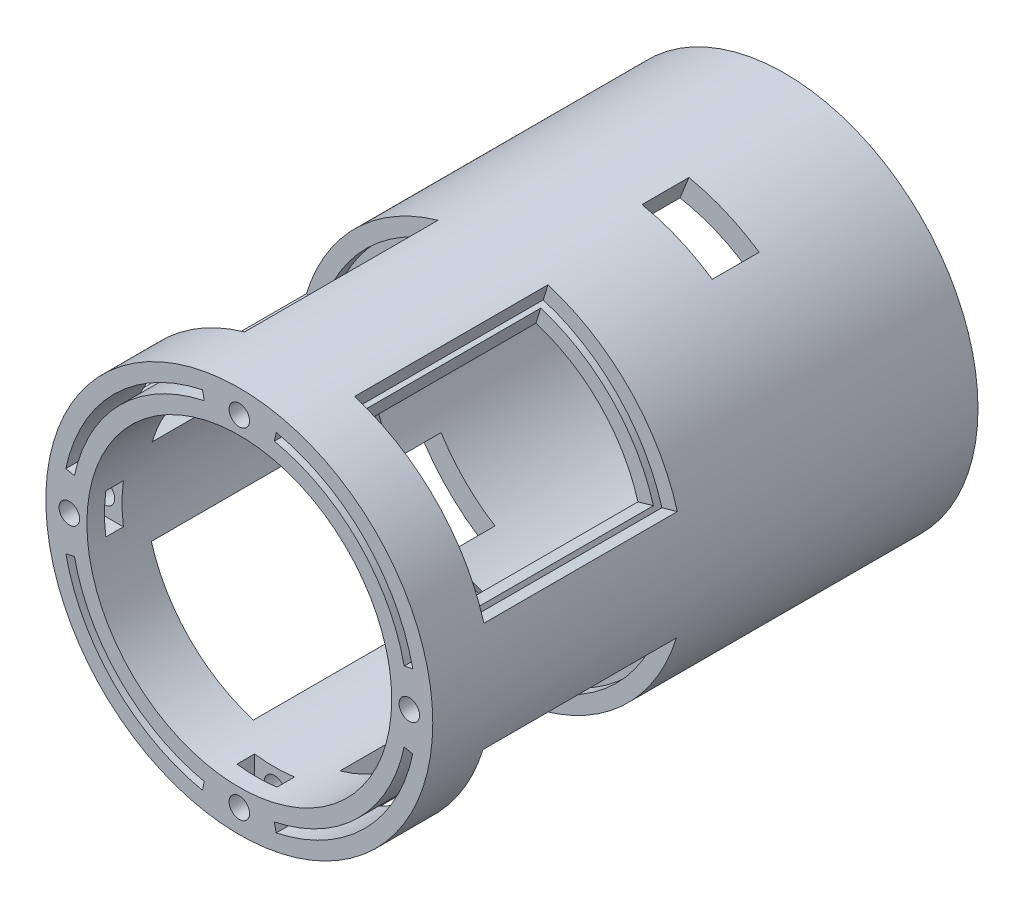
SolidWorks part; units mm, degrees
material "PEI"
ref_plane "Alzado" through (0, 0, 0) normal (0, 0, 1) x (1, 0, 0)
ref_plane "Planta" through (0, 0, 0) normal (0, 1, 0) x (1, 0, 0)
ref_plane "Vista lateral" through (0, 0, 0) normal (1, 0, 0) x (0, 0, -1)
sketch "Croquis1" plane through (0, 0, 0) normal (0, 0, 1) x (1, 0, 0)
  circle A0 centre (0, 0) radius 33
  circle A1 centre (0, 0) radius 29
  dimension "D1" = 66
  dimension "D2" = 4
extrude "Boss-Extrude1" add sketch "Croquis1" along normal blind 93
ref_axis "Eje1" through (0, 0, 93) along (0, 0, -1)
ref_plane "Plano2" through (0, 0, 0) normal (0.9563, -0.2924, 0) x (0, 0, -1)
sketch "Sketch8" plane through (0, 0, 0) normal (0, 0, -1) x (-1, 0, 0)
  arc A0 (-4, -28.7228) -> (4, -28.7228) centre (0, 0) ccw
  circle A1 centre (0, 0) radius 29 construction
  arc A2 (-4, -28.7228) -> (4, -28.7228) centre (0, -30.3008) cw
  arc A3 (-28.7228, 4) -> (-28.7228, -4) centre (0, 0) ccw
  arc A4 (-28.7228, 4) -> (-28.7228, -4) centre (-30.3008, 0) cw
  arc A5 (4, 28.7228) -> (-4, 28.7228) centre (0, 0) ccw
  arc A6 (4, 28.7228) -> (-4, 28.7228) centre (0, 30.3008) cw
  arc A7 (28.7228, -4) -> (28.7228, 4) centre (0, 0) ccw
  arc A8 (28.7228, -4) -> (28.7228, 4) centre (30.3008, 0) cw
  point P8 (0, -26.0008)
  point P20 (0, 0)
  dimension "D1" = 4.3
  dimension "D2" = 8
  dimension "D3" = 4
extrude "Boss-Extrude4" add sketch "Sketch8" against normal blind 15
sketch "Sketch9" plane through (0, 0, 0) normal (0, 0, -1) x (-1, 0, 0)
  circle A0 centre (0, -29) radius 1.75
  circle A1 centre (0, 0) radius 29 construction
  circle A2 centre (0, 0) radius 33 construction
  circle A3 centre (-29, 0) radius 1.75
  circle A4 centre (0, 29) radius 1.75
  circle A5 centre (29, 0) radius 1.75
  point P16 (0, 0)
  dimension "D1" = 4
  dimension "D2" = 3.5
  dimension "D3" = 4
extrude "Cut-Extrude3" cut sketch "Sketch9" against normal blind 14
ref_plane "Mid plane" through (0, 0, 46.5) normal (0, 0, 1) x (1, 0, 0)
ref_plane "Plano para USB y Switch" through (-23.3345, -23.3345, 0) normal (-0.7071, -0.7071, 0) x (0, 0, -1)
sketch "Sketch10" plane through (-23.3345, -23.3345, 0) normal (-0.7071, -0.7071, 0) x (0, 0, -1)
  line L0 (0, -33) -> (0, 33) construction
  line L1 (-10.5, 7.5) -> (-3.5, 7.5)
  line L2 (-10.5, 7.5) -> (-10.5, -7.5)
  line L3 (-10.5, -7.5) -> (-3.5, -7.5)
  line L4 (-3.5, 7.5) -> (-3.5, -7.5)
  line L5 (-10.5, 7.5) -> (-3.5, -7.5) construction
  line L6 (-10.5, -7.5) -> (-3.5, 7.5) construction
  line L8 (-42, 6.5) -> (-34, 6.5)
  line L9 (-42, 6.5) -> (-42, -6.5)
  line L10 (-42, -6.5) -> (-34, -6.5)
  line L11 (-34, 6.5) -> (-34, -6.5)
  line L12 (-42, 6.5) -> (-34, -6.5) construction
  line L13 (-42, -6.5) -> (-34, 6.5) construction
  point P0 (-7, 0)
  point P9 (-38, 0)
  dimension "D1" = 7
  dimension "D2" = 15
  dimension "D3" = 7
  dimension "D4" = 13
  dimension "D5" = 8
  dimension "D6" = 38
extrude "Corte USB y Switch" cut sketch "Sketch10" against normal blind 10
ref_plane "Plano USB PCB_C" through (12.362, 30.5971, 0) normal (0.3746, 0.9272, 0) x (0, 0, -1)
sketch "Sketch11" plane through (12.362, 30.5971, 0) normal (0.3746, 0.9272, 0) x (0, 0, -1)
  line L0 (0, -33) -> (0, 33) construction
  line L1 (-30.9, 6) -> (-22.9, 6)
  line L2 (-30.9, 6) -> (-30.9, -7)
  line L3 (-30.9, -7) -> (-22.9, -7)
  line L4 (-22.9, 6) -> (-22.9, -7)
  line L5 (-30.9, 6) -> (-22.9, -7) construction
  line L6 (-30.9, -7) -> (-22.9, 6) construction
  point P0 (-26.9, -0.5)
  dimension "D1" = 0.5
  dimension "D2" = 8
  dimension "D3" = 13
  dimension "D4" = 22.9
extrude "Cut-Extrude5" cut sketch "Sketch11" against normal blind 10
ref_plane "Plano3" through (0, 0, 3) normal (0, 0, -1) x (-1, 0, 0)
sketch "Tuerca" plane through (0, 0, 3) normal (0, 0, -1) x (-1, 0, 0)
  line L30 (-29, -3.4064) -> (-25.5799, -3.4064)
  line L31 (-29, -3.4064) -> (-26.05, -1.7032) construction
  line L32 (-26.05, -1.7032) -> (-26.05, 1.7032) construction
  line L33 (-26.05, 1.7032) -> (-29, 3.4064) construction
  line L34 (-29, 3.4064) -> (-31.95, 1.7032)
  line L35 (-31.95, 1.7032) -> (-31.95, -1.7032)
  line L36 (-31.95, -1.7032) -> (-29, -3.4064)
  line L37 (-29, 3.4064) -> (-25.5799, 3.4064)
  circle A10 centre (-29, 0) radius 2.95 construction
  arc A12 (-25.5799, -3.4064) -> (-25.5799, 3.4064) centre (-28.2041, 0) ccw
  dimension "D4" = 5.9
extrude "Alojamiento tuerca" cut sketch "Tuerca" against normal blind 3 contours L30 A12 L37 L34 L35 L36 region at (27.8612, 0, 3)
pattern_circular "Alojamientos Tuercas Superior" count 4 over 360 about axis through (0, 0, 0) along (0, 0, 1) of "Alojamiento tuerca"
sketch "Sketch13" plane through (0, 0, 93) normal (0, 0, 1) x (1, 0, 0)
  circle A0 centre (0, 0) radius 29
  circle A1 centre (0, 0) radius 26
  circle A3 centre (0, 0) radius 29 construction
  circle A4 centre (0, 0) radius 33 construction
  dimension "D1" = 52
  dimension "D2" = 7
extrude "Grosor adicional" add sketch "Sketch13" against normal blind 48
sketch "Corte Revolucion" plane through (0, 0, 0) normal (0.9563, -0.2924, 0) x (0, 0, -1)
  line L0 (-83, 33) -> (-83, 25)
  line L1 (-30.9, 33) -> (-93, 33) construction
  line L2 (-83, 25) -> (-50, 25)
  line L4 (-50, 33) -> (-83, 33)
  line L5 (-97, 29) -> (-42, 29) construction
  line L6 (-93, 33) -> (-93, -33) construction
  line L14 (-50, 25) -> (-50, 33)
  dimension "D1" = 8
  dimension "D6" = 10
revolve "Cut-Revolve3" cut sketch "Corte Revolucion" angle 57 about axis through (0, 0, 93) along (0, 0, -1)
pattern_circular "CirPattern3" count 4 over 360 about axis through (0, 0, 0) along (0, 0, 1) of "Cut-Revolve3"
sketch "Croquis2" plane through (0, 0, 93) normal (0, 0, 1) x (1, 0, 0)
  line L0 (0, 0) -> (-6.2893, -29.589) construction
  line L1 (0, 0) -> (-29.589, -6.2893) construction
  line L2 (0, 0) -> (0, -30.5) construction
  line L3 (0, 0) -> (-30.5, 0) construction
  line L4 (-29.589, -6.2893) -> (-28.1217, -5.9775)
  line L5 (-6.2893, -29.589) -> (-5.9775, -28.1217)
  line L6 (-29.589, 6.2893) -> (-28.1217, 5.9775)
  line L7 (-6.2893, 29.589) -> (-5.9775, 28.1217)
  line L8 (6.2893, 29.589) -> (5.9775, 28.1217)
  line L9 (29.589, 6.2893) -> (28.1217, 5.9775)
  line L10 (29.589, -6.2893) -> (28.1217, -5.9775)
  line L11 (6.2893, -29.589) -> (5.9775, -28.1217)
  circle A0 centre (0, 0) radius 28.75 construction
  circle A1 centre (0, 0) radius 30.25 construction
  circle A3 centre (0, 0) radius 29.5 construction
  arc A4 (-6.2893, -29.589) -> (-29.589, -6.2893) centre (0, 0) cw
  arc A5 (-5.9775, -28.1217) -> (-28.1217, -5.9775) centre (0, 0) cw
  arc A6 (-29.589, 6.2893) -> (-6.2893, 29.589) centre (0, 0) cw
  arc A7 (-28.1217, 5.9775) -> (-5.9775, 28.1217) centre (0, 0) cw
  arc A8 (6.2893, 29.589) -> (29.589, 6.2893) centre (0, 0) cw
  arc A9 (5.9775, 28.1217) -> (28.1217, 5.9775) centre (0, 0) cw
  arc A10 (29.589, -6.2893) -> (6.2893, -29.589) centre (0, 0) cw
  arc A11 (28.1217, -5.9775) -> (5.9775, -28.1217) centre (0, 0) cw
  circle A13 centre (0, 0) radius 33 construction
  circle A14 centre (0, 0) radius 26 construction
  point P4 (-6.1334, -28.8554)
  point P32 (0, 0)
  dimension "D3" = 12
  dimension "D4" = 12
  dimension "D1" = 1.5
  dimension "D2" = 7
  dimension "D6" = 3.5
  dimension "D5" = 4
extrude "Corte postizos" cut sketch "Croquis2" against normal blind 45
chamfer "Chamfer3" distance 3 angle 45 1 edges at (29, 0, 45)
sketch "Sketch14" plane through (0, 0, 93) normal (0, 0, 1) x (1, 0, 0)
  circle A0 centre (29, 0) radius 1.75
  circle A1 centre (-29, 0) radius 1.75
  circle A2 centre (0, 29) radius 1.75
  circle A3 centre (0, -29) radius 1.75
  circle A4 centre (29, 0) radius 1.75 construction
  point P12 (0, 0)
extrude "Tornillos Inferiores" cut sketch "Sketch14" against normal blind 15
mirror "Mirror3" about plane through (0, 0, 46.5) normal (0, 0, 1) of "Alojamientos Tuercas Superior"
sketch "Sketch16" plane through (0, 0, 0) normal (0, 0, -1) x (-1, 0, 0)
  line L0 (4, -28.7228) -> (6.9459, -28.1559) construction
  line L1 (4, -28.7228) -> (3.2441, -24.7949)
  line L2 (6.9459, -28.1559) -> (6.19, -24.228)
  line L3 (3.2441, -24.7949) -> (6.19, -24.228)
  arc A0 (4, -28.7228) -> (6.9459, -28.1559) centre (5.473, -28.4393) ccw
  circle A1 centre (0, 0) radius 29 construction
  point P3 (0, 0)
  point P10 (0, 0)
  dimension "D1" = 1.5
  dimension "D2" = 4
  dimension "D3" = 3
extrude "Cut-Extrude9" cut sketch "Sketch16" against normal blind 45
chamfer "Chamfer4" distance 1.5 angle 45 3 edges at (-3.7161, -27.2476, 45) (-6.6621, -26.6807, 45) (-5.7564, -29.9123, 45)
equation "\"D6@Croquis2\"=\"D2@Croquis2\"/2"
